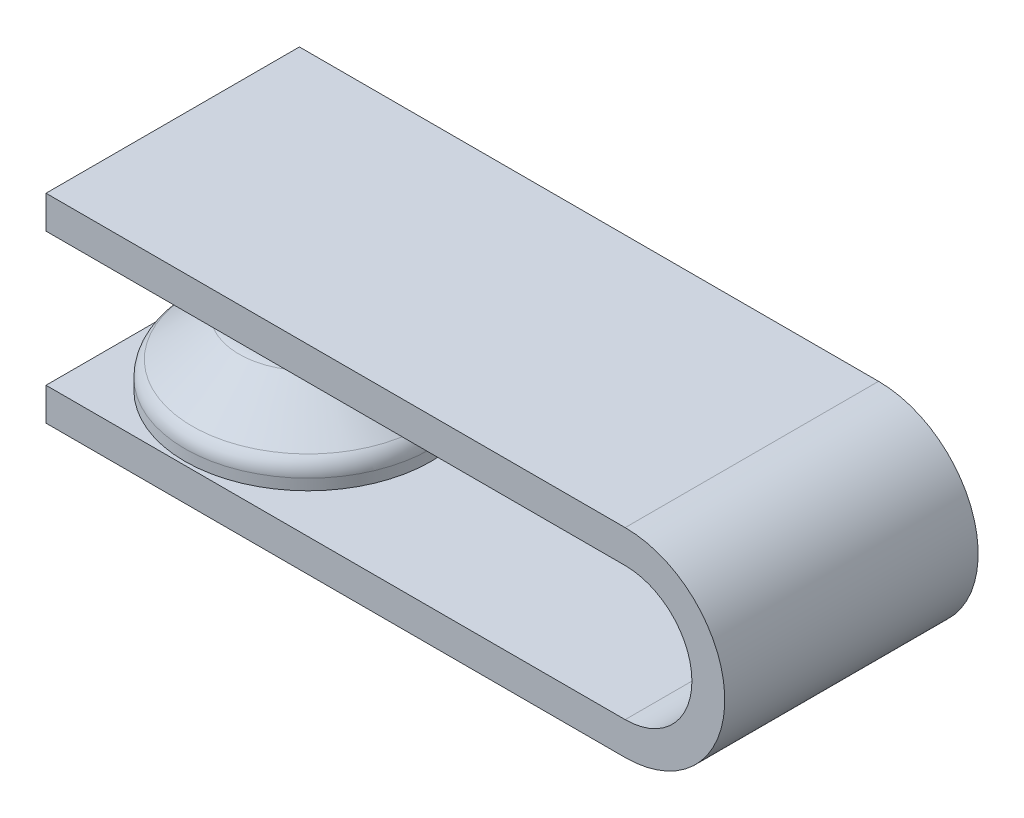
SolidWorks part; units mm, degrees
ref_plane "Front Plane" through (0, 0, 0) normal (0, 0, 1) x (1, 0, 0)
ref_plane "Top Plane" through (0, 0, 0) normal (0, 1, 0) x (1, 0, 0)
ref_plane "Right Plane" through (0, 0, 0) normal (1, 0, 0) x (0, 0, -1)
sketch "Sketch1" plane through (0, 0, 0) normal (0, 0, 1) x (1, 0, 0)
  line L0 (0, 5) -> (0, 0) construction
  line L1 (0, 5) -> (-3, 5) construction
  line L2 (-3, 5) -> (-3, 2.5) construction
  line L3 (-3, 2.5) -> (-6, 0) construction
  line L4 (-6, 0) -> (0, 0) construction
  line L5 (-6, 0) -> (-6, -1)
  line L6 (-6, -1) -> (0, -1)
  line L7 (0, -1) -> (0, 5)
  line L8 (0, 5) -> (-3, 5)
  line L9 (-3, 5) -> (-3, 2.5)
  line L10 (-3, 2.5) -> (-6, 0)
  dimension "D1" = 3
  dimension "D2" = 5
  dimension "D3" = 6
  dimension "D4" = 2.5
  dimension "D5" = 1
revolve "Revolve1" add sketch "Sketch1" angle 360 about L7 region at (-2.2424, 1.5202, 0)
fillet "Fillet1" radius 1 3 edges at (3, 5, 0) (3, 2.5, 0) (6, 0, 0)
sketch "Sketch2" plane through (0, -1, 0) normal (0, -1, 0) x (1, 0, 0)
  line L1 (-6.5932, -6.1707) -> (6.5932, -6.1707)
  line L2 (-6.5932, -6.1707) -> (-6.5932, 6.1707)
  line L3 (-6.5932, 6.1707) -> (6.5932, 6.1707)
  line L4 (6.5932, -6.1707) -> (6.5932, 6.1707)
  line L5 (-6.5932, -6.1707) -> (6.5932, 6.1707) construction
  line L6 (-6.5932, 6.1707) -> (6.5932, -6.1707) construction
  point P0 (0, 0)
  point P6 (7.39, 7.485)
  point P7 (6.5932, 6.1707)
extrude "Boss-Extrude1" add sketch "Sketch2" along normal blind 1.6
extrude "Boss-Extrude2" add sketch "Sketch2<2>" against normal blind 1.6 from offset 6.5 separate body offset against normal yes
sketch "Sketch2<2>" plane through (0, -1, 0) normal (0, -1, 0) x (1, 0, 0) same geometry as "Sketch2"
sketch "Sketch4" plane through (0, 0, 6.1707) normal (0, 0, 1) x (1, 0, 0)
  line L0 (6.5932, 5.5) -> (21.6164, 5.5)
  line L1 (6.5932, -2.6) -> (21.6164, -2.6)
  line L2 (6.5932, -2.6) -> (6.5932, 7.1) construction
  line L3 (6.5932, 7.1) -> (21.6164, 7.1)
  line L4 (21.6164, -2.6) -> (21.6164, 7.1) construction
  line L5 (6.5932, -1) -> (21.6164, -1)
  line L6 (6.5932, 5.5) -> (6.5932, 7.1)
  line L7 (6.5932, -1) -> (6.5932, -2.6)
  arc A0 (21.6164, 7.1) -> (21.6164, -2.6) centre (21.6164, 2.25) cw
  arc A1 (21.6164, 5.5) -> (21.6164, -1) centre (21.6164, 2.25) cw
  point P13 (6.5932, 7.1)
extrude "Boss-Extrude3" add sketch "Sketch4" against normal up to surface (12.3414 mm away) up to face at (0, 6.3, -6.1707)
